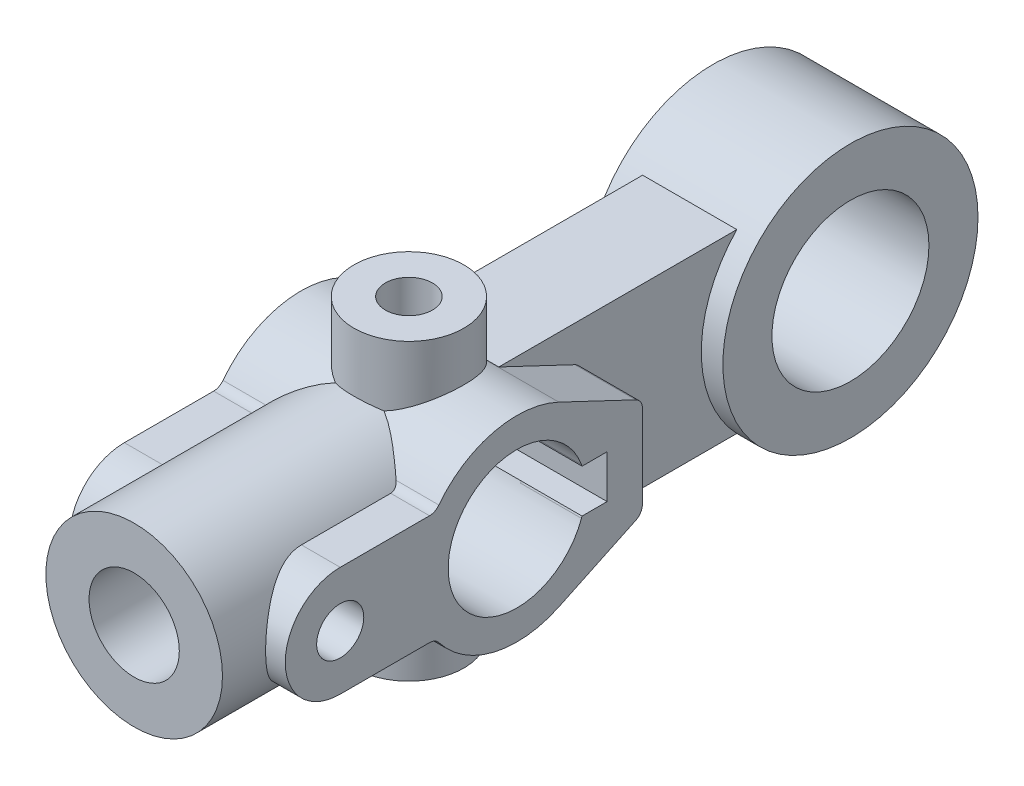
SolidWorks part; units mm, degrees
ref_plane "Front Plane" through (0, 0, 0) normal (0, 0, 1) x (1, 0, 0)
ref_plane "Top Plane" through (0, 0, 0) normal (0, 1, 0) x (1, 0, 0)
ref_plane "Right Plane" through (0, 0, 0) normal (1, 0, 0) x (0, 0, -1)
sketch "Sketch1" plane through (0, 0, 0) normal (0, 0, 1) x (1, 0, 0)
  line L0 (-11.5, 0) -> (-22.5, 0)
  line L1 (11.5, 0) -> (22.5, 0)
  arc A0 (11.5, 0) -> (-11.5, 0) centre (0, 0) ccw
  arc A1 (22.5, 0) -> (-22.5, 0) centre (0, 0) ccw
  dimension "D1" = 11.5
  dimension "D2" = 22.5
extrude "Boss-Extrude1" add sketch "Sketch1" along normal blind 70
ref_plane "Plane1" through (0, 37.5, 0) normal (0, 1, 0) x (1, 0, 0)
sketch "Sketch2" plane through (0, 37.5, 0) normal (0, 1, 0) x (1, 0, 0)
  line L0 (14, 0) -> (6, 0)
  line L1 (-6, 0) -> (-14, 0)
  arc A0 (-6, 0) -> (6, 0) centre (0, 0) ccw
  arc A1 (-14, 0) -> (14, 0) centre (0, 0) ccw
  dimension "D1" = 6
  dimension "D2" = 14
extrude "Boss-Extrude3" add sketch "Sketch2" against normal up to body separate body
sketch "Sketch4" plane through (0, 37.5, 0) normal (0, 1, 0) x (1, 0, 0)
  line L0 (6, 0) -> (-6, 0)
  arc A0 (-6, 0) -> (6, 0) centre (0, 0) ccw
extrude "Cut-Extrude1" cut sketch "Sketch4" against normal blind 70
ref_plane "Plane2" through (27.5, 0, 0) normal (1, 0, 0) x (0, 0, -1)
sketch "Sketch5" plane through (27.5, 0, 0) normal (1, 0, 0) x (0, 0, -1)
  line L2 (-45, 14) -> (-22.2486, 14)
  line L3 (0, 25) -> (0, 17.5)
  line L4 (-59, 0) -> (-51, 0)
  line L5 (-39, 0) -> (-17.5, 0)
  arc A0 (-39, 0) -> (-51, 0) centre (-45, 0) ccw
  arc A1 (-45, 14) -> (-59, 0) centre (-45, 0) ccw
  arc A2 (0, 17.5) -> (-17.5, 0) centre (0, 0) ccw
  arc A3 (0, 25) -> (-19.8648, 15.1786) centre (0, 0) ccw
  arc A5 (-22.2486, 14) -> (-19.8648, 15.1786) centre (-22.2486, 17) ccw
  dimension "D1" = 3
  dimension "D2" = 6
  dimension "D3" = 14
  dimension "D4" = 17.5
  dimension "D5" = 25
  dimension "D6" = 45
extrude "Boss-Extrude4" add sketch "Sketch5" against normal up to body separate body
sketch "Sketch6" plane through (27.5, 0, 0) normal (1, 0, 0) x (0, 0, -1)
  line L0 (0, 0) -> (0, 17.5)
  line L1 (0, 0) -> (-17.5, 0)
  line L2 (-51, 0) -> (-39, 0)
  arc A0 (-39, 0) -> (-51, 0) centre (-45, 0) ccw construction
  arc A1 (-39, 0) -> (-51, 0) centre (-45, 0) ccw
  arc A2 (0, 17.5) -> (-17.5, 0) centre (0, 0) ccw
extrude "Cut-Extrude2" cut sketch "Sketch6" against normal blind 70
ref_plane "Plane3" through (-27.5, 0, 0) normal (1, 0, 0) x (0, 0, -1)
sketch "Sketch7" plane through (-27.5, 0, 0) normal (1, 0, 0) x (0, 0, -1)
  line L0 (-45, 14) -> (-22.2486, 14)
  line L1 (-59, 0) -> (-51, 0)
  line L2 (-39, 0) -> (-31, 0)
  line L3 (-25, 0) -> (-17.5, 0)
  line L4 (0, 17.5) -> (0, 25)
  line L5 (-31, 0) -> (-25, 0)
  arc A0 (0, 25) -> (-19.8648, 15.1786) centre (0, 0) ccw
  arc A1 (0, 17.5) -> (-17.5, 0) centre (0, 0) ccw
  arc A2 (-39, 0) -> (-51, 0) centre (-45, 0) ccw
  arc A3 (-45, 14) -> (-59, 0) centre (-45, 0) ccw
  arc A4 (-22.2486, 14) -> (-19.8648, 15.1786) centre (-22.2486, 17) ccw
  dimension "D1" = 3
  dimension "D2" = 25
  dimension "D3" = 6
extrude "Boss-Extrude5" add sketch "Sketch7" along normal up to body separate body
ref_plane "Plane4" through (0, 0, 0) normal (0, 0, 1) x (1, 0, 0)
sketch "Sketch8" plane through (0, 0, 0) normal (0, 0, 1) x (1, 0, 0)
  circle A0 centre (0, 0) radius 11.5
  circle A1 centre (0, 0) radius 22.5
  dimension "D1" = 23
  dimension "D2" = 45
extrude "Boss-Extrude6" add sketch "Sketch8" against normal blind 35
sketch "Sketch9" plane through (-27.5, 0, 0) normal (1, 0, 0) x (0, 0, -1)
  line L6 (0, 17.5) -> (0, 25)
  line L7 (23, 0) -> (32, 0)
  line L8 (23, 0) -> (23, 5.5)
  line L9 (23, 5.5) -> (16.6132, 5.5)
  line L10 (32, 0) -> (32, 10.6019)
  line L11 (30.2848, 13.3129) -> (10.7064, 22.5914)
  arc A7 (16.6132, 5.5) -> (0, 17.5) centre (0, 0) ccw
  arc A8 (10.7064, 22.5914) -> (0, 25) centre (0, 0) ccw
  arc A9 (32, 10.6019) -> (30.2848, 13.3129) centre (29, 10.6019) ccw
  dimension "D1" = 3
  dimension "D2" = 17.5
  dimension "D3" = 10.7064
  dimension "D4" = 16.6132
  dimension "D5" = 23
  dimension "D6" = 29
sketch "Sketch10" plane through (0, 37.5, 0) normal (0, 1, 0) x (1, 0, 0)
  line L0 (-14, 0) -> (-6, 0)
  line L1 (6, 0) -> (14, 0)
  arc A0 (6, 0) -> (-6, 0) centre (0, 0) ccw
  arc A1 (14, 0) -> (-14, 0) centre (0, 0) ccw
extrude "Boss-Extrude7" add sketch "Sketch10" against normal up to body separate body
extrude "Boss-Extrude8" add sketch "Sketch9" along normal up to body separate body
sketch "Sketch12" plane through (-27.5, 0, 0) normal (1, 0, 0) x (0, 0, -1)
  line L0 (16.6132, 5.5) -> (23, 5.5)
  line L1 (23, 5.5) -> (23, 0)
  line L2 (23, 0) -> (17.5, 0)
  arc A0 (16.6132, 5.5) -> (17.5, 0) centre (0, 0) ccw
extrude "Cut-Extrude3" cut sketch "Sketch12" along normal through all both and the other way through all
sketch "Sketch13" plane through (0, 37.5, 0) normal (0, 1, 0) x (1, 0, 0)
  circle A0 centre (0, 0) radius 6
  circle A1 centre (0, 0) radius 14 construction
  dimension "D1" = 12
extrude "Cut-Extrude4" cut sketch "Sketch13" against normal blind 32
sketch "Sketch14" plane through (0, 0, -35) normal (0, 0, -1) x (-1, 0, 0)
  line L0 (0, 0) -> (34.5196, 0)
  line L1 (34.5196, 0) -> (34.5196, -29.0888)
  line L2 (34.5196, -29.0888) -> (-33.3024, -29.0888)
  line L3 (-33.3024, -29.0888) -> (-33.3024, 0)
  line L4 (-33.3024, 0) -> (0, 0)
  circle A0 centre (0, 0) radius 11.5 construction
  dimension "D1" = 34.5196
  dimension "D2" = 33.3024
  dimension "D3" = 29.0888
extrude "Cut-Extrude5" cut sketch "Sketch14" against normal through all
sketch "Sketch15" plane through (0, 0, -35) normal (0, 0, -1) x (-1, 0, 0)
  line L0 (-22.5, 0) -> (-11.5, 0)
  line L1 (11.5, 0) -> (22.5, 0)
  arc A0 (22.5, 0) -> (-22.5, 0) centre (0, 0) ccw
  arc A1 (11.5, 0) -> (-11.5, 0) centre (0, 0) ccw
extrude "Cut-Extrude6" cut sketch "Sketch15" against normal blind 21
sketch "Sketch16" plane through (27.5, 0, 0) normal (1, 0, 0) x (0, 0, -1)
  line L0 (0, 0) -> (62.5, 0)
  circle A0 centre (95, 0) radius 20
  circle A1 centre (95, 0) radius 32.5
  dimension "D1" = 40
  dimension "D2" = 65
  dimension "D3" = 62.5
extrude "Boss-Extrude9" add sketch "Sketch16" against normal blind 45 separate body contours A1 A0 region at (27.5, -31.5808, -95)
sketch "Sketch18" plane through (27.5, 0, 0) normal (1, 0, 0) x (0, 0, -1)
  circle A0 centre (95, 0) radius 20
  circle A1 centre (95, 0) radius 32.5
  circle A2 centre (95, 0) radius 20 construction
  dimension "D1" = 40
  dimension "D2" = 65
extrude "Cut-Extrude7" cut sketch "Sketch18" against normal blind 10
sketch "Sketch19" plane through (0, 0, -14) normal (0, 0, -1) x (-1, 0, 0)
  line L0 (-12, 22.5) -> (0, 22.5)
  line L2 (-12, 22.5) -> (-12, 0)
  line L3 (-12, 0) -> (12, 0)
  line L4 (12, 0) -> (12, 22.5)
  line L5 (12, 22.5) -> (0, 22.5)
  dimension "D1" = 7.8997
extrude "Boss-Extrude10" add sketch "Sketch19" along normal up to body and the other way blind 14 separate body
sketch "Sketch21" plane through (-27.5, 0, 0) normal (-1, 0, 0) x (0, 0, 1)
  line L0 (-23, 0) -> (-32, 0)
  line L1 (-32, 0) -> (-32, 10.6019)
  line L2 (-32, 10.6019) -> (-30.2848, 13.3129)
  line L3 (-30.2848, 13.3129) -> (-10.7064, 22.5914)
  line L5 (-23, 0) -> (-23, 5.5)
  line L6 (-23, 5.5) -> (-16.6132, 5.5)
  line L7 (0, 25) -> (0, 17.5)
  arc A1 (0, 17.5) -> (-16.6132, 5.5) centre (0, 0) ccw
  arc A2 (0, 25) -> (-10.7064, 22.5914) centre (0, 0) ccw
extrude "Boss-Extrude11" add sketch "Sketch21" against normal up to surface (15.5 mm away) up to face at (-12, 14.1992, -23.7264)
sketch "Sketch22" plane through (0, 0, 0) normal (0, 0, 1) x (1, 0, 0)
  line L1 (32.2367, 0) -> (32.2367, -39.8499)
  line L2 (32.2367, -39.8499) -> (-33.0522, -39.8499)
  line L3 (-33.0522, -39.8499) -> (-33.0522, 0)
  line L4 (-33.0522, 0) -> (0, 0)
  line L5 (0, 0) -> (0, 50.0531)
  line L6 (0, 50.0531) -> (32.2367, 50.0531)
  line L7 (32.2367, 50.0531) -> (32.2367, 0)
  dimension "D1" = 32.2367
  dimension "D2" = 33.0522
  dimension "D3" = 50.0531
  dimension "D4" = 39.8499
extrude "Cut-Extrude10" cut sketch "Sketch22" against normal through all both and the other way through all
sketch "Sketch24" plane through (0, 37.5, 0) normal (0, 1, 0) x (1, 0, 0)
  circle A0 centre (0, 0) radius 6
  dimension "D1" = 12
extrude "Cut-Extrude11" cut sketch "Sketch24" against normal through all both and the other way through all
sketch "Sketch25" plane through (-27.5, 0, 0) normal (-1, 0, 0) x (0, 0, 1)
  line L0 (-23, 0) -> (-23, 5.5)
  line L1 (-23, 5.5) -> (-16.6132, 5.5)
  line L2 (-16.6132, 5.5) -> (-23, 5.5) construction
  line L3 (-23, 0) -> (0, 0)
  line L4 (0, 0) -> (0, 17.5)
  arc A0 (17.5, 0) -> (-16.6132, 5.5) centre (0, 0) ccw construction
  arc A1 (0, 17.5) -> (-16.6132, 5.5) centre (0, 0) ccw
extrude "Cut-Extrude12" cut sketch "Sketch25" against normal through all both and the other way through all
sketch "Sketch26" plane through (-27.5, 0, 0) normal (-1, 0, 0) x (0, 0, 1)
  line L0 (-32, 0) -> (-32, 10.6019)
  line L1 (-32, 0) -> (-23, 0)
  line L2 (-23, 0) -> (-23, 5.5)
  line L3 (-23, 5.5) -> (-16.6132, 5.5)
  line L4 (-16.6132, 5.5) -> (-10.7064, 22.5914)
  line L5 (-10.7064, 22.5914) -> (-30.2848, 13.3129)
  arc A1 (-30.2848, 13.3129) -> (-32, 10.6019) centre (-29, 10.6019) ccw
extrude "Boss-Extrude12" add sketch "Sketch26" against normal up to surface (15.5 mm away) up to face at (-12, 11.6317, -39.5091)
mirror "Mirror1" about plane through (27.502, 0, -23) normal (0, 1, 0) of bodies 124
mirror "Mirror2" about plane through (0, 0, -127.5) normal (-1, 0, 0) of bodies 125
